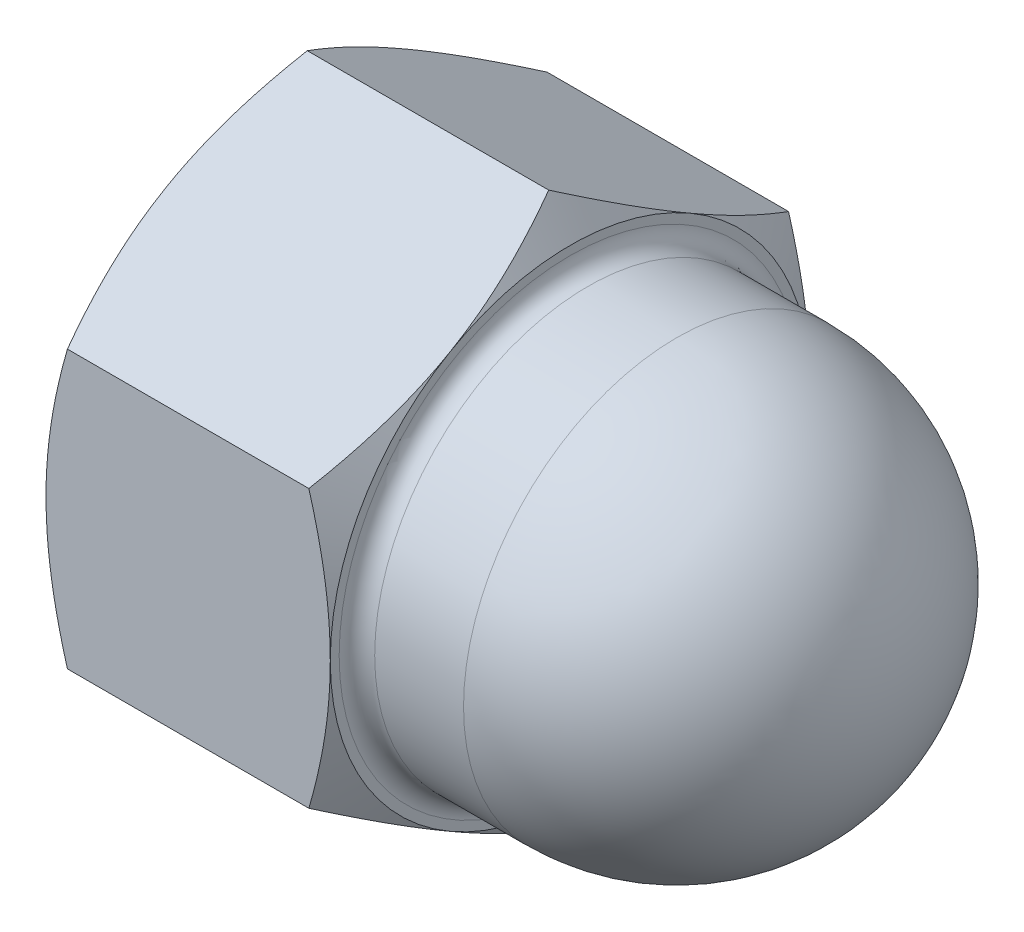
SolidWorks part; units mm, degrees
extrude "BaseNut" add sketch "BaseNutSke" along normal blind 16
sketch "BaseNutSke" plane through (0, 0, 0) normal (1, 0, 0) x (0, 0, -1)
  line L6 (13.5, 7.7942) -> (13.5, -7.7942)
  line L7 (-13.5, 7.7942) -> (-13.5, -7.7942)
  line L8 (13.5, 7.7942) -> (0, 15.5885)
  line L9 (0, 15.5885) -> (-13.5, 7.7942)
  line L10 (-13.5, -7.7942) -> (0, -15.5885)
  line L11 (0, -15.5885) -> (13.5, -7.7942)
  dimension "D4" = 60
  dimension "D1" = 120
  dimension "D2" = 13.5
  dimension "D3" = 13.5
  dimension "Width_flats" = 27
revolve "DoubleChamfer" cut sketch "Sketch4" angle 360 about L10 other way angle 118
sketch "Sketch4" plane through (0, 0, 0) normal (0, 0, 1) x (1, 0, 0)
  line L0 (0, 13.5) -> (2.5048, 17.8385)
  line L1 (16, 13.5) -> (13.4952, 17.8385)
  line L2 (2.5048, 17.8385) -> (13.4952, 17.8385)
  line L3 (16, 13.5) -> (18, 13.5)
  line L4 (18, 13.5) -> (18, 28.5)
  line L5 (18, 28.5) -> (-2, 28.5)
  line L6 (0, 13.5) -> (-2, 13.5)
  line L7 (-2, 13.5) -> (-2, 28.5)
  line L8 (16, 15.5885) -> (16, 7.7942) construction
  line L9 (0, 15.5885) -> (0, 7.7942) construction
  line L10 (0, 0) -> (57.15, 0) construction
  line L11 (16, 15.5885) -> (0, 15.5885) construction
  point P17 (16, 13.5)
  dimension "D1" = 30
  dimension "D2" = 30
  dimension "D3" = 2
  dimension "D4" = 2
  dimension "D5" = 2.25
  dimension "D6" = 15
  dimension "D7" = 13.5
revolve "TapDrill" cut sketch "TapDriSke"
sketch "TapDriSke" plane through (0, 0, 0) normal (0, 0, 1) x (1, 0, 0)
  line L0 (0, 0) -> (44.45, 0) construction
  line L1 (0, 8.75) -> (27, 8.75)
  line L2 (0, 0) -> (0, -11.6913) construction
  line L3 (27, 8.75) -> (32.2575, 0)
  line L4 (0, 0) -> (63.5, 0) construction
  line L5 (32.2575, 0) -> (0, 0)
  line L6 (0, 0) -> (0, 8.75)
  line L7 (27, -8.75) -> (32.2575, 0) construction
  line L8 (0, -8.75) -> (27, -8.75) construction
  line L9 (0.5, 6.35) -> (0.5, 3.175) construction
  dimension "Drill_depth" = 27
cosmetic thread "ThreadCosmetic" [suppressed]
revolve "EndChamfer" cut sketch "EndChamferSketch" angle 360 about L4 other way angle 70
sketch "EndChamferSketch" plane through (0, 0, 0) normal (0, 0, 1) x (1, 0, 0)
  line L0 (-0.0254, 10) -> (0.0254, 10)
  line L1 (0.0254, 10) -> (0.9882, 8.625)
  line L2 (0.9882, 8.625) -> (-0.0254, 8.625)
  line L3 (-0.0254, 8.625) -> (-0.0254, 10)
  line L4 (0, 0) -> (-15.875, 0) construction
  dimension "D1" = 0.0508
  dimension "D2" = 35
  dimension "D3" = 0.0254
  dimension "ChamferDepth" = 1.375
  dimension "ThreadMajor" = 10
ref_plane "Plane1" through (0, 0, 0) normal (0, 0, 1) x (1, 0, 0)
ref_plane "Plane2" through (0, 0, 0) normal (0, 1, 0) x (1, 0, 0)
ref_plane "Plane3" through (0, 0, 0) normal (1, 0, 0) x (0, 0, -1)
sketch "DomeSke" plane through (0, 0, 0) normal (0, 0, 1) x (1, 0, 0)
  line L0 (0, 0) -> (63.5, 0) construction
  line L1 (0, 7.7942) -> (0, -7.7942) construction
  line L2 (34, 0) -> (0, 0)
  line L3 (0, 12) -> (22, 12)
  line L4 (0, -12) -> (22.225, -12) construction
  line L5 (0, 12) -> (0, 0)
  arc A0 (22, 12) -> (34, 0) centre (22, 0) cw
revolve "Dome" add sketch "DomeSke" angle 360 about L0
sketch "GrvSke" plane through (0, 0, 0) normal (0, 0, 1) x (1, 0, 0)
  line L0 (0, 0) -> (38.1, 0) construction
  line L1 (16, 10.5) -> (16, 7.75)
  line L2 (16, 7.75) -> (23, 7.75)
  line L3 (23, 7.75) -> (23, 10.5)
  line L4 (23, 10.5) -> (16, 10.5)
  line L5 (16, 0) -> (16, 11.6913) construction
  line L6 (27, 8.75) -> (0, 8.75) construction
  dimension "D1" = 1
revolve "Groove" cut sketch "GrvSke" angle 360 about L0
sketch "ThdSchSke" plane through (0, 0, 0) normal (0, 1, 0) x (1, 0, 0)
  line L0 (0.0381, 10) -> (-0.8372, 8.75)
  line L1 (-0.8372, 8.75) -> (-0.8372, 4.375)
  line L2 (-0.8372, 4.375) -> (0.9134, 4.375)
  line L3 (0.9134, 4.375) -> (0.9134, 8.75)
  line L4 (0.9134, 8.75) -> (0.0381, 10)
  line L5 (-38.1, 0) -> (3.175, 0) construction
  line L6 (0, 0) -> (-15.875, 0) construction
  line L7 (0, 0) -> (63.5, 0) construction
  line L9 (2.5381, 0.475) -> (2.5381, -5.875) construction
  dimension "D1" = 0.0381
  dimension "Thread_major" = 20
  dimension "Tap_drill" = 17.5
  dimension "OverCut" = 8.75
revolve "ThreadSchematic" [suppressed] cut sketch "ThdSchSke" angle 360 about L5
pattern_linear "ThdSchPat" [suppressed]
fillet "DomeFillet" radius 1 1 edges at (16, 0, -12)
equation "' \"Width_flats@BaseNutSke\" = 27"
equation "' \"Hex_ht@BaseNut\" = 16"
equation "' \"Overall_ht@DomeSke\" = 34"
equation "' \"Dome_rad@DomeSke\" = 12"
equation "' \"Thread_min@TapDriSke\" = 17.5"
equation "' \"Drill_clr@TapDriSke\" = 1.0"
equation "' \"Advance@ThdSchSke\" = 2.5"
equation "' \"Thread_nominal@ThreadCosmetic\" = 20"
equation "' \"Radius@DomeFillet\" = 1.0"
equation "' \"Groove_wid@GrvSke\" = 7"
equation "\"Drill_depth@TapDriSke\" = \"Overall_ht@DomeSke\"  - \"Drill_clr@TapDriSke\" - 0.3 * \"Thread_nominal@ThreadCosmetic\""
equation "\"Groove_dia@GrvSke\" = \"Thread_nominal@ThreadCosmetic\" * 1.05"
equation "\"Thread_depth@ThreadCosmetic\" = \"Thread_nominal@ThreadCosmetic\""
equation "\"D2@BaseNutSke\" = \"Width_flats@BaseNutSke\" / 2"
equation "\"D3@BaseNutSke\" = \"Width_flats@BaseNutSke\" / 2"
equation "\"D7@Sketch4\" = \"Width_flats@BaseNutSke\" / 2"
equation "\"D5@Sketch4\" = \"Width_flats@BaseNutSke\" / 12"
equation "\"Thread_major@ThdSchSke\" = \"Thread_nominal@ThreadCosmetic\""
equation "\"Tap_drill@ThdSchSke\" = \"Thread_min@TapDriSke\""
equation "\"OverCut@ThdSchSke\" = \"Tap_drill@ThdSchSke\" * 0.5"
equation "\"Num_threads@ThdSchPat\" = int(  ( \"Hex_ht@BaseNut\" - 0.002 ) / \"Advance@ThdSchSke\" + 0.999 )  + 1"
equation "' \"Num_threads@ThdSchPat\" = int(  ( \"Thread_depth@ThreadCosmetic\" - 0.002 ) / \"Advance@ThdSchSke\" + 0.999 )  + 1"
equation "\"Advance@ThdSchPat\" = ( \"Hex_ht@BaseNut\" - 0.002 ) /  (\"Num_threads@ThdSchPat\" - 1) 'relax it"
equation "' \"Advance@ThdSchPat\" = ( \"Thread_depth@ThreadCosmetic\" - 0.002 ) /  (\"Num_threads@ThdSchPat\" - 1) 'relax it"
equation "\"ThreadMajor@EndChamferSketch\" = \"Thread_nominal@ThreadCosmetic\" * 0.5"
equation "\"ChamferDepth@EndChamferSketch\" = (\"Thread_nominal@ThreadCosmetic\" - \"Thread_min@TapDriSke\") * 0.55"
